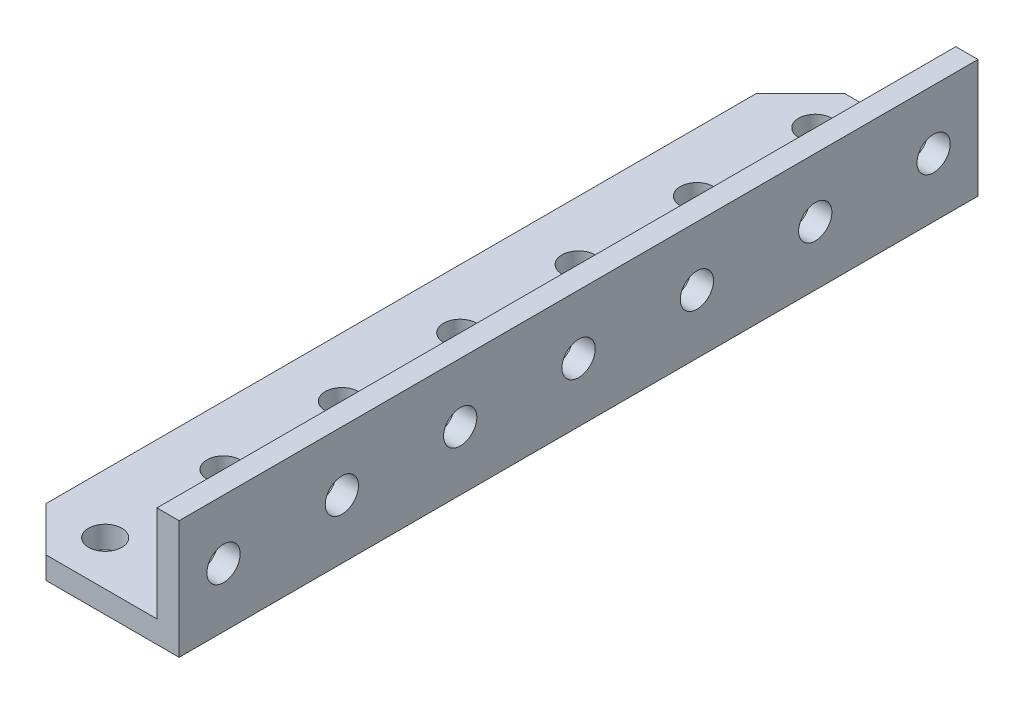
SolidWorks part; units mm, degrees
material "AISI Type 316L stainless steel"
ref_plane "Front Plane" through (0, 0, 0) normal (0, 0, 1) x (1, 0, 0)
ref_plane "Top Plane" through (0, 0, 0) normal (0, 1, 0) x (1, 0, 0)
ref_plane "Right Plane" through (0, 0, 0) normal (1, 0, 0) x (0, 0, -1)
sketch "Sketch1" plane through (0, 0, 0) normal (0, 0, 1) x (1, 0, 0)
  line L0 (0, 0) -> (38.1, 0)
  line L1 (38.1, 0) -> (38.1, 25.4)
  line L2 (38.1, 25.4) -> (33.3375, 25.4)
  line L3 (33.3375, 25.4) -> (33.3375, 4.7625)
  line L4 (33.3375, 4.7625) -> (0, 4.7625)
  line L5 (0, 4.7625) -> (0, 0)
  dimension "D1" = 38.1
  dimension "D2" = 25.4
  dimension "D3" = 4.7625
extrude "Boss-Extrude1" add sketch "Sketch1" along normal blind 177.8 contours L4 L5 L0 L1 L2 L3
sketch "Sketch6" plane through (0, 4.7625, 0) normal (0, 1, 0) x (1, 0, 0)
  line L0 (12.7, -177.8) -> (12.7, 0) construction
  line L1 (33.3375, -177.8) -> (0, -177.8) construction
  line L2 (33.3375, 0) -> (0, 0) construction
  line L6 (12.7, -165.1) -> (12.7, -139.7) construction
  line L7 (0, -177.8) -> (0, 0) construction
  point P8 (12.7, -165.1)
  point P38 (12.7, -139.7)
  point P39 (12.7, -114.3)
  point P40 (12.7, -88.9)
  point P41 (12.7, -63.5)
  point P42 (12.7, -38.1)
  point P43 (12.7, -12.7)
  dimension "D1" = 12.7
  dimension "D2" = 12.7
  dimension "D4" = 25.4
  dimension "D3" = 7
hole_wizard "1/4 Clearance Hole1" positions "Sketch6" profile "Sketch7" hole size "1/4" standard "ANSI Inch" end condition up to next
sketch "Sketch7" plane through (12.7, 4.7625, 12.7) normal (1, 0, 0) x (0, 0, 1)
  line L0 (0, 0) -> (0, 4.7625)
  line L1 (0, 4.7625) -> (3.5712, 4.7625)
  line L2 (3.5712, 4.7625) -> (3.5712, 0)
  line L5 (3.5712, 0) -> (0, 0)
  line L11 (0, -6.35) -> (0, 107.95) construction
  dimension "Thru Hole Dia." = 7.1425
  dimension "Thru Hole Depth" = 4.7625
sketch "Sketch8" plane through (33.3375, 0, 0) normal (-1, 0, 0) x (0, 0, 1)
  line L0 (0, 12.7) -> (177.8, 12.7) construction
  line L1 (0, 25.4) -> (0, 4.7625) construction
  line L4 (12.7, 12.7) -> (38.1, 12.7) construction
  line L6 (177.8, 25.4) -> (0, 25.4) construction
  line L7 (177.8, 25.4) -> (177.8, 4.7625) construction
  point P6 (12.7, 12.7)
  point P26 (38.1, 12.7)
  point P27 (63.5, 12.7)
  point P28 (88.9, 12.7)
  point P29 (114.3, 12.7)
  point P30 (139.7, 12.7)
  point P31 (165.1, 12.7)
  point P32 (190.5, 12.7)
  dimension "D1" = 12.7
  dimension "D3" = 25.4
  dimension "D4" = 12.7
  dimension "D2" = 8
hole_wizard "1/4 Clearance Hole2" positions "Sketch8" profile "Sketch9" hole size "1/4" standard "ANSI Inch" end condition up to next
sketch "Sketch9" plane through (33.3375, 12.7, 190.5) normal (0, 1, 0) x (0, 0, 1)
  line L0 (0, 0) -> (0, 4.7625)
  line L1 (0, 4.7625) -> (3.5712, 4.7625)
  line L2 (3.5712, 4.7625) -> (3.5712, 0)
  line L5 (3.5712, 0) -> (0, 0)
  line L11 (0, -6.35) -> (0, 107.95) construction
  dimension "Thru Hole Dia." = 7.1425
  dimension "Thru Hole Depth" = 4.7625
chamfer "Chamfer1" distance 12.7 angle 45 2 edges at (0, 2.3813, 177.8) (0, 2.3813, 0)
ref_plane "Plane1" through (0, 0, 88.9) normal (0, 0, -1) x (-1, 0, 0)
sketch "Sketch10" plane through (0, 0, 0) normal (0, 0, -1) x (-1, 0, 0)
  line L1 (-38.1, 25.4) -> (0, 25.4)
  line L2 (-38.1, 25.4) -> (-38.1, 0)
  line L3 (-38.1, 0) -> (0, 0)
  line L4 (0, 25.4) -> (0, 0)
extrude "Cut-Extrude1" cut sketch "Sketch10" against normal blind 3.175
mirror "Mirror1" about plane through (0, 0, 88.9) normal (0, 0, -1) of "Cut-Extrude1"
